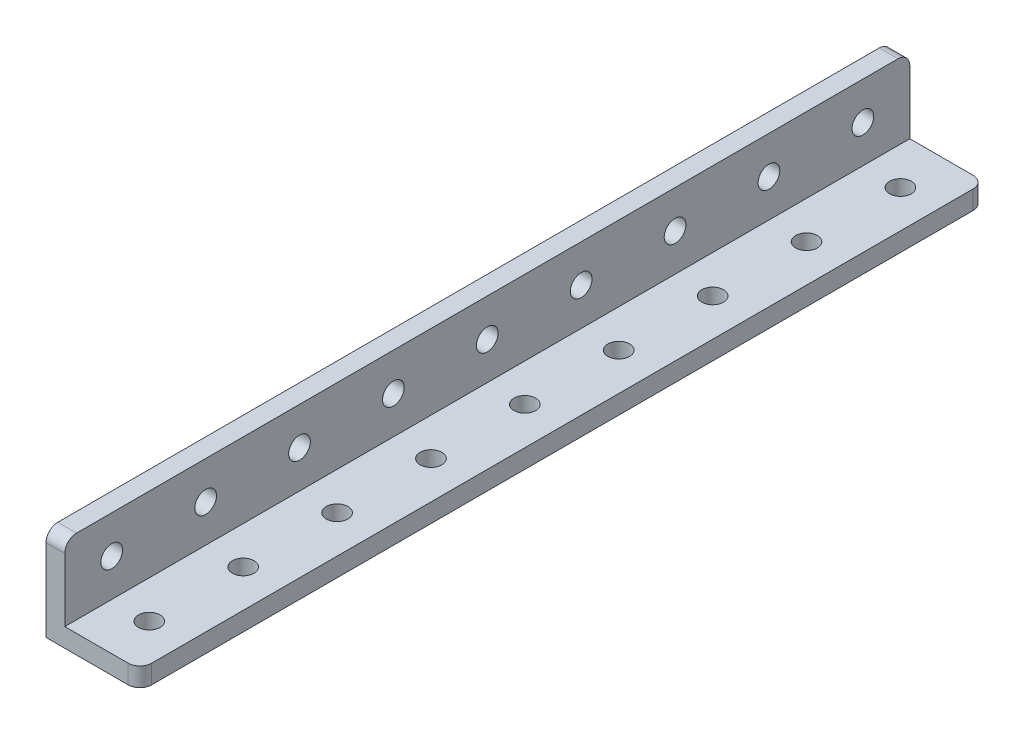
SolidWorks part; units mm, degrees
material "2024 Alloy"
ref_plane "Front Plane" through (0, 0, 0) normal (0, 0, 1) x (1, 0, 0)
ref_plane "Top Plane" through (0, 0, 0) normal (0, 1, 0) x (1, 0, 0)
ref_plane "Right Plane" through (0, 0, 0) normal (1, 0, 0) x (0, 0, -1)
ref_plane "Plane1" through (16, 0, 0) normal (1, 0, 0) x (0, 0, -1)
sketch "Sketch1" plane through (16, 0, 0) normal (1, 0, 0) x (0, 0, -1)
  line L0 (0, 0) -> (144, 0)
  line L1 (144, 0) -> (144, 16)
  line L2 (144, 16) -> (0, 16)
  line L3 (0, 16) -> (0, 0)
extrude "Boss-Extrude1" add sketch "Sketch1" against normal blind 16
sketch "Sketch2" plane through (0, 0, 0) normal (0, 0, 1) x (1, 0, 0)
  line L0 (3.2, 3.2) -> (16, 3.2)
  line L1 (16, 3.2) -> (16, 16)
  line L2 (16, 16) -> (3.2, 16)
  line L3 (3.2, 16) -> (3.2, 3.2)
extrude "Cut-Extrude1" cut sketch "Sketch2" against normal through all
hole_wizard "Ø3.7 (3.7) Diameter Hole1" positions "Sketch4" profile "Sketch3" hole size "Ø3.7" standard "ANSI Metric"
sketch "Sketch4" plane through (0, 0, 0) normal (-1, 0, 0) x (0, 0, 1)
  point P0 (-24, 9.6)
  point P1 (-40, 9.6)
  point P2 (-56, 9.6)
  point P3 (-72, 9.6)
  point P4 (-88, 9.6)
  point P5 (-104, 9.6)
  point P6 (-120, 9.6)
  point P7 (-136, 9.6)
  point P8 (-8, 9.6)
sketch "Sketch3" plane through (0, 9.6, -24) normal (0, 1, 0) x (0, 0, 1)
  line L0 (0, 0) -> (0, 16)
  line L1 (0, 16) -> (1.85, 16)
  line L2 (1.85, 16) -> (1.85, 0)
  line L5 (1.85, 0) -> (0, 0)
  line L11 (0, -6.35) -> (0, 107.95) construction
  dimension "Thru Hole Dia." = 3.7
  dimension "Thru Hole Depth" = 16
hole_wizard "Ø3.7 (3.7) Diameter Hole2" positions "Sketch6" profile "Sketch5" hole size "Ø3.7" standard "ANSI Metric"
sketch "Sketch6" plane through (0, 0, 0) normal (0, -1, 0) x (-1, 0, 0)
  point P0 (-9.6, 24)
  point P1 (-9.6, 40)
  point P2 (-9.6, 56)
  point P3 (-9.6, 72)
  point P4 (-9.6, 88)
  point P5 (-9.6, 104)
  point P6 (-9.6, 120)
  point P7 (-9.6, 136)
  point P8 (-9.6, 8)
sketch "Sketch5" plane through (9.6, 0, -24) normal (1, 0, 0) x (0, 0, -1)
  line L0 (0, 0) -> (0, 16)
  line L1 (0, 16) -> (1.85, 16)
  line L2 (1.85, 16) -> (1.85, 0)
  line L5 (1.85, 0) -> (0, 0)
  line L11 (0, -6.35) -> (0, 107.95) construction
  dimension "Thru Hole Dia." = 3.7
  dimension "Thru Hole Depth" = 16
fillet "Fillet1" radius 2 4 edges at (1.6, 16, -144) (1.6, 16, 0) (16, 1.6, -144) (16, 1.6, 0) tangent propagation no
